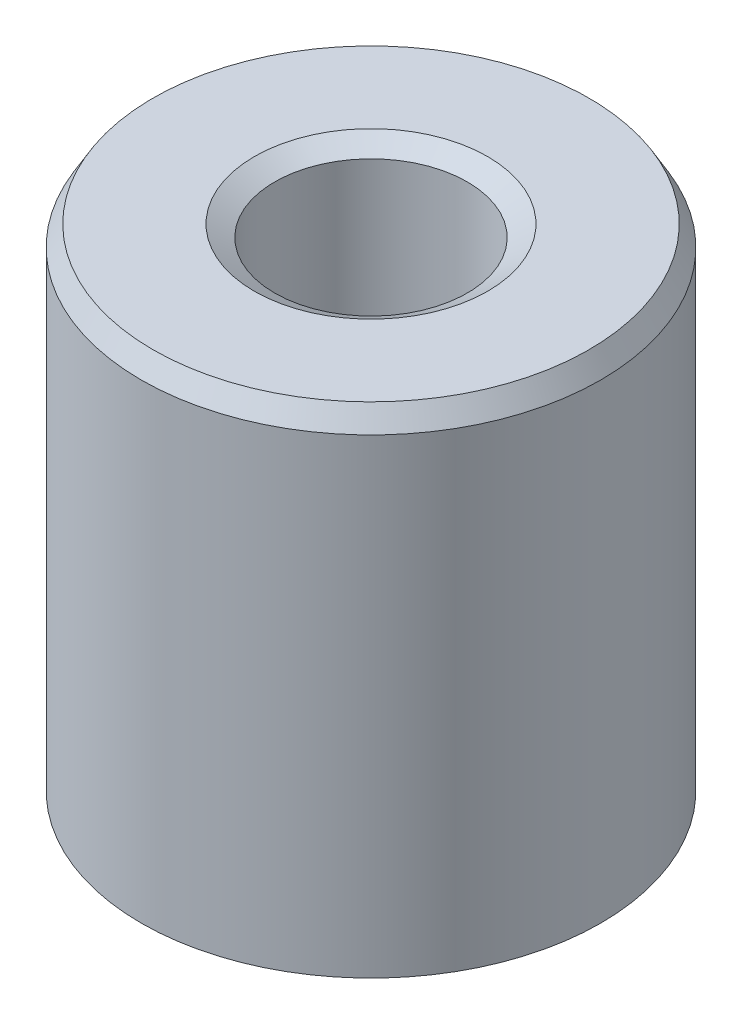
SolidWorks part; units mm, degrees
ref_plane "Front Plane" through (0, 0, 0) normal (0, 0, 1) x (1, 0, 0)
ref_plane "Top Plane" through (0, 0, 0) normal (0, 1, 0) x (1, 0, 0)
ref_plane "Right Plane" through (0, 0, 0) normal (1, 0, 0) x (0, 0, -1)
sketch "Sketch1" plane through (0, 0, 0) normal (0, 1, 0) x (1, 0, 0)
  circle A0 centre (0, 0) radius 37.5
  dimension "SLEEVE_OD" = 75
extrude "Boss-Extrude1" add sketch "Sketch1" along normal blind 82.0251
sketch "Sketch2" plane through (0, 0, 0) normal (0, 1, 0) x (1, 0, 0)
  circle A0 centre (0, 0) radius 15.7254
  dimension "BORE_D" = 31.4507
extrude "Cut-Extrude1" cut sketch "Sketch2" along normal through all
chamfer "Chamfer1" distance 3.3202 angle 30 4 edges at (0, 82.0251, 15.7254) (0, 0, 15.7254) (0, 0, 37.5) (0, 82.0251, 37.5) first distance on face at (0, 82.0251, 15.7254) first distance on face at (0, 0, 15.7254) first distance on face at (0, 82.0251, 37.5)
